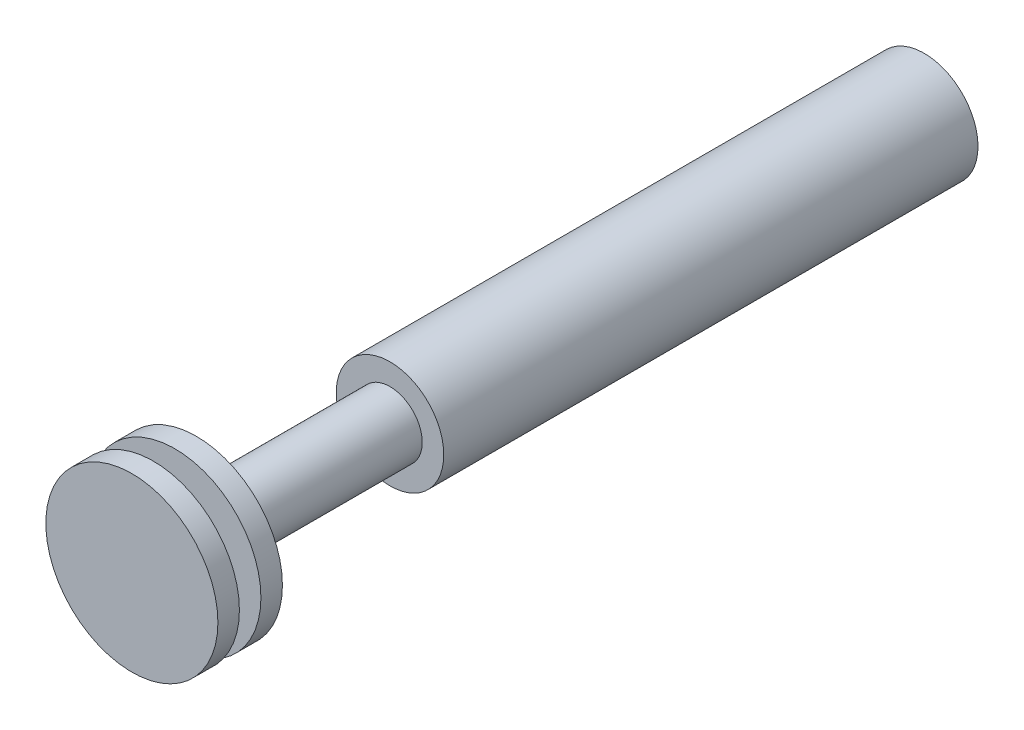
SolidWorks part; units mm, degrees
ref_plane "前视基准面" through (0, 0, 0) normal (0, 0, 1) x (1, 0, 0)
ref_plane "上视基准面" through (0, 0, 0) normal (0, 1, 0) x (1, 0, 0)
ref_plane "右视基准面" through (0, 0, 0) normal (1, 0, 0) x (0, 0, -1)
other "Configuration Table"
sketch "草图1" plane through (0, 0, 0) normal (0, 0, 1) x (1, 0, 0)
  circle A0 centre (0, 0) radius 3
extrude "凸台-拉伸1" add sketch "草图1" along normal blind 180
sketch "草图2" plane through (0, 0, 180) normal (0, 0, 1) x (1, 0, 0)
  circle A2 centre (0, 0) radius 8
  circle A3 centre (0, 0) radius 8
  dimension "D1" = 5
extrude "凸台-拉伸2" add sketch "草图2" against normal blind 2
extrude "凸台-拉伸3" add sketch "草图2<2>" along normal blind 2 from surface starting at face at (3, 0, 0)
sketch "草图2<2>" plane through (0, 0, 180) normal (0, 0, 1) x (1, 0, 0) same geometry as "草图2"
extrude "凸台-拉伸4" add sketch "草图1<2>" against normal blind 2
sketch "草图1<2>" plane through (0, 0, 0) normal (0, 0, 1) x (1, 0, 0) same geometry as "草图1"
extrude "凸台-拉伸5" add sketch "草图1<3>" along normal blind 2 from surface starting at face at (8, 0, 180)
sketch "草图1<3>" plane through (0, 0, 0) normal (0, 0, 1) x (1, 0, 0) same geometry as "草图1"
extrude "凸台-拉伸6" add sketch "草图2<3>" along normal blind 2 from surface starting at face at (3, 0, 182)
sketch "草图2<3>" plane through (0, 0, 180) normal (0, 0, 1) x (1, 0, 0) same geometry as "草图2"
extrude "凸台-拉伸7" add sketch "草图2<4>" against normal blind 2 from surface starting at face at (3, 0, -2)
sketch "草图2<4>" plane through (0, 0, 180) normal (0, 0, 1) x (1, 0, 0) same geometry as "草图2"
sketch "草图3" plane through (0, 0, 184) normal (0, 0, 1) x (1, 0, 0)
  circle A0 centre (0, 0) radius 5
extrude "凸台-拉伸10" add sketch "草图3" against normal blind 60 from offset 64 offset against normal yes
sketch "草图4" plane through (0, 0, 0) normal (1, 0, 0) x (0, 0, -1)
  line L1 (19.1288, 22.8607) -> (-110.3208, 22.8607)
  line L2 (19.1288, 22.8607) -> (19.1288, -22.3367)
  line L3 (19.1288, -22.3367) -> (-110.3208, -22.3367)
  line L4 (-110.3208, 22.8607) -> (-110.3208, -22.3367)
extrude "切除-拉伸1" cut sketch "草图4" against normal through all both and the other way through all
sketch "草图5" plane through (0, 0, 120) normal (0, 0, 1) x (1, 0, 0)
  circle A1 centre (0, 0) radius 5
  circle A2 centre (0, 0) radius 5
  dimension "D1" = 0
extrude "凸台-拉伸11" add sketch "草图5" along normal blind 20
extrude "凸台-拉伸12" add sketch "草图5<2>" along normal blind 40
sketch "草图5<2>" plane through (0, 0, 120) normal (0, 0, 1) x (1, 0, 0) same geometry as "草图5"
